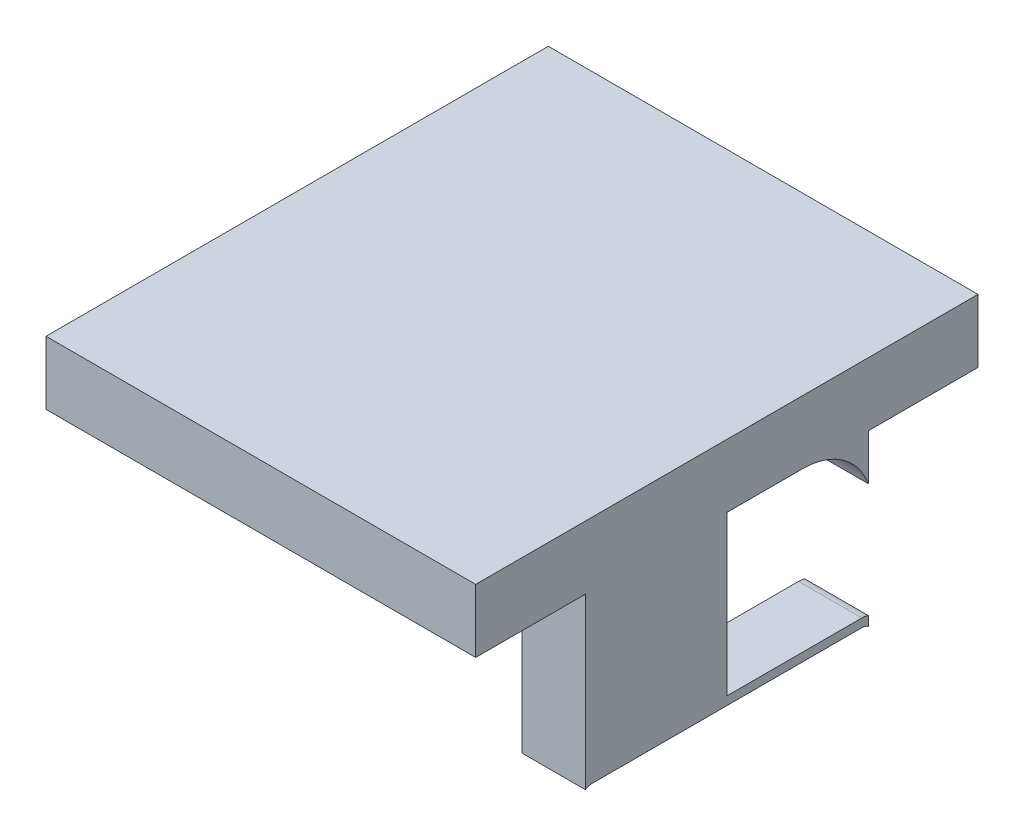
SolidWorks part; units mm, degrees
note: The reader was unsure of these and kept them because the rebuilt part matched: shared geometry of "Sketch1<3>".
ref_plane "Front Plane" through (0, 0, 0) normal (0, 0, 1) x (1, 0, 0)
ref_plane "Top Plane" through (0, 0, 0) normal (0, 1, 0) x (1, 0, 0)
ref_plane "Right Plane" through (0, 0, 0) normal (1, 0, 0) x (0, 0, -1)
sketch "Sketch1" plane through (-157.8546, 0, 0) normal (1, 0, 0) x (0, 0, -1)
  line L0 (42.7806, -79.36) -> (42.7806, -66.6234) construction
  line L1 (30.8806, -66.6234) -> (42.7806, -66.6234)
  line L2 (30.8806, -66.6234) -> (30.8806, -65.1234)
  line L3 (30.8806, -65.1234) -> (42.7806, -65.1234)
  line L4 (42.7806, -66.6234) -> (42.7806, -65.1234)
  line L5 (40.0306, -70.3868) -> (33.6306, -70.3868) construction
  line L6 (40.0306, -70.3868) -> (33.6306, -70.3868)
  line L7 (33.4806, -66.6234) -> (33.4806, -70.6368)
  line L8 (40.1806, -66.6234) -> (40.1806, -70.6368)
  line L9 (36.8306, -66.6234) -> (36.8306, -73.96) construction
  line L10 (36.8306, -66.6234) -> (36.8306, -73.96) construction
  line L11 (36.9806, -68.2734) -> (36.9806, -70.5868)
  line L12 (40.0306, -70.5868) -> (33.6306, -70.5868) construction
  line L13 (40.0306, -70.5868) -> (33.6306, -70.5868)
  arc A0 (40.4806, -70.8368) -> (40.0306, -70.3868) centre (40.0306, -70.8368) ccw construction
  arc A1 (33.6306, -70.3868) -> (33.1806, -70.8368) centre (33.6306, -70.8368) ccw construction
  arc A2 (40.4806, -70.8368) -> (40.0306, -70.3868) centre (40.0306, -70.8368) ccw
  arc A3 (33.6306, -70.3868) -> (33.1806, -70.8368) centre (33.6306, -70.8368) ccw
  arc A4 (40.2806, -70.8368) -> (40.0306, -70.5868) centre (40.0306, -70.8368) ccw construction
  arc A5 (33.6306, -70.5868) -> (33.3806, -70.8368) centre (33.6306, -70.8368) ccw construction
  arc A6 (40.2806, -70.8368) -> (40.0306, -70.5868) centre (40.0306, -70.8368) ccw
  arc A7 (33.6306, -70.5868) -> (33.3806, -70.8368) centre (33.6306, -70.8368) ccw
  circle A8 centre (38.6306, -68.2734) radius 1.65 construction
  circle A9 centre (38.6306, -68.2734) radius 1.65
  line M8 (33.3806, -66.6234) -> (30.8806, -66.6234)
  line M12 (42.7806, -66.6234) -> (40.2806, -66.6234)
  dimension "D1" = 1.5
  dimension "D2" = 0.1
extrude "Boss-Extrude1" add sketch "Sketch1" against normal up to surface (1.5 mm away) contours L10 L1 L7 A3 L6 | L1 L10 L6 A2 L8 | L4 L3 L2 L1 M12 M8 | A9 L8 L1 | L10 L6 A3 L7 A7 L13 | L6 L10 L13 L11
extrude "Boss-Extrude2" add sketch "Sketch1<3>" against normal up to surface (10.18 mm away) contours L4 L3 L2 L1 M12 M8
sketch "Sketch1<3>" plane through (-157.8546, 0, 0) normal (1, 0, 0) x (0, 0, -1) same geometry as "Sketch1"
sketch "Sketch2" plane through (0, -66.6234, 0) normal (0, -1, 0) x (1, 0, 0)
  line L0 (-167.1846, -34.9806) -> (-166.1846, -34.9806)
  line L1 (-166.1846, -34.9806) -> (-166.1846, -33.4806)
  line L2 (-166.1846, -33.4806) -> (-164.6846, -33.4806)
  line L3 (-164.6846, -33.4806) -> (-164.6846, -32.4806)
  line L4 (-164.6846, -32.4806) -> (-167.1846, -32.4806)
  line L5 (-167.1846, -32.4806) -> (-167.1846, -34.9806)
  line L6 (-161.9546, -41.1806) -> (-159.4546, -41.1806)
  line L10 (-159.4546, -40.2806) -> (-161.9546, -40.2806)
  line L11 (-161.9546, -40.2806) -> (-161.9546, -41.1806)
  line L12 (-167.2846, -32.3806) -> (-167.1846, -32.4806) construction
  line L13 (-159.4546, -41.1806) -> (-159.3546, -41.1806)
  line L14 (-167.2846, -32.3806) -> (-159.3546, -32.3806) construction
  line L15 (-159.4546, -41.1806) -> (-159.4546, -40.2806)
  line L16 (-159.3546, -41.2806) -> (-159.3546, -40.2806) construction
  line L18 (-159.4546, -41.1806) -> (-159.3546, -41.2806) construction
  line L20 (-159.3546, -41.1806) -> (-159.3546, -40.2806)
  line L21 (-159.3546, -40.2806) -> (-159.4546, -40.2806)
  line L22 (-159.3546, -40.2806) -> (-157.8546, -40.2806) construction
  dimension "D1" = 0.1
  dimension "D2" = 1
  dimension "D3" = 1.5
extrude "Boss-Extrude3" add sketch "Sketch2" along normal blind 1
ref_plane "Plane1" through (-75.8957, 0, 64.9259) normal (-0.7599, 0, 0.6501) x (0.6501, 0, 0.7599)
